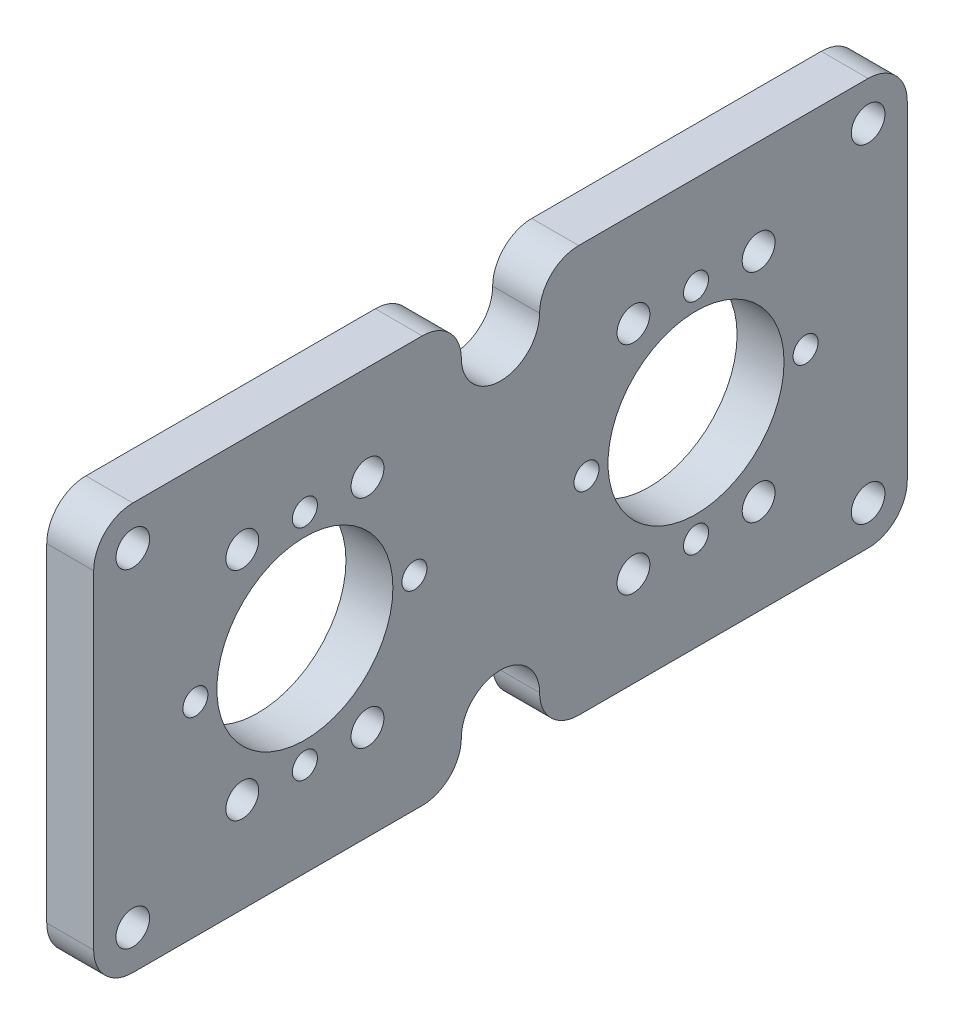
SolidWorks part; units mm, degrees
material "6061-T6 (SS)"
ref_plane "前视基准面" through (0, 0, 0) normal (0, 0, 1) x (1, 0, 0)
ref_plane "上视基准面" through (0, 0, 0) normal (0, 1, 0) x (1, 0, 0)
ref_plane "右视基准面" through (0, 0, 0) normal (1, 0, 0) x (0, 0, -1)
other "Configuration Table"
sketch "草图1" plane through (0, 0, 0) normal (1, 0, 0) x (0, 0, -1)
  line L0 (0, 0) -> (420, 0) construction
  line L1 (0, 0) -> (0, 110) construction
  line L2 (0, 110) -> (420, 110) construction
  line L3 (420, 110) -> (420, 0) construction
  line L4 (0, 15) -> (420, 15) construction
  line L5 (210, 110) -> (210, 0) construction
  line L6 (220.1351, 41.0331) -> (270.1351, 41.0331) construction
  line L7 (220.1351, 64.1271) -> (200.1351, 52.5801) construction
  line L8 (200.1351, 52.5801) -> (200.1351, 29.4861) construction
  line L9 (200.1351, 29.4861) -> (220.1351, 17.9391) construction
  line L10 (220.1351, 17.9391) -> (240.1351, 29.4861) construction
  line L11 (240.1351, 29.4861) -> (240.1351, 52.5801) construction
  line L12 (240.1351, 52.5801) -> (220.1351, 64.1271) construction
  line L13 (270.1351, 64.1271) -> (250.1351, 52.5801) construction
  line L14 (250.1351, 52.5801) -> (250.1351, 29.4861) construction
  line L15 (250.1351, 29.4861) -> (270.1351, 17.9391) construction
  line L16 (270.1351, 17.9391) -> (290.1351, 29.4861) construction
  line L17 (290.1351, 29.4861) -> (290.1351, 52.5801) construction
  line L18 (290.1351, 52.5801) -> (270.1351, 64.1271) construction
  line L19 (55.5, 52) -> (220.1351, 41.0331) construction
  line L20 (270.1351, 41.0331) -> (364.5, 52) construction
  line L21 (56.7695, 71.0578) -> (221.4046, 60.0909) construction
  line L22 (218.8656, 21.9754) -> (54.2305, 32.9422) construction
  line L23 (267.9302, 60.0054) -> (362.2951, 70.9723) construction
  line L24 (366.7049, 33.0277) -> (272.3401, 22.0608) construction
  line L30 (220.1351, 17.9391) -> (240.1351, 29.4861) construction
  line L31 (240.1351, 29.4861) -> (240.1351, 52.5801) construction
  line L32 (240.1351, 52.5801) -> (220.1351, 64.1271) construction
  line L33 (220.1351, 64.1271) -> (200.1351, 52.5801) construction
  line L34 (200.1351, 52.5801) -> (200.1351, 29.4861) construction
  line L35 (200.1351, 29.4861) -> (220.1351, 17.9391) construction
  line L36 (270.1351, 17.9391) -> (290.1351, 29.4861) construction
  line L37 (290.1351, 29.4861) -> (290.1351, 52.5801) construction
  line L38 (290.1351, 52.5801) -> (270.1351, 64.1271) construction
  line L39 (270.1351, 64.1271) -> (250.1351, 52.5801) construction
  line L40 (250.1351, 52.5801) -> (250.1351, 29.4861) construction
  line L41 (250.1351, 29.4861) -> (270.1351, 17.9391) construction
  line L42 (297.1351, 15.0331) -> (193.1351, 15.0331)
  line L43 (297.1351, 15.0331) -> (297.1351, 67.0331)
  line L44 (297.1351, 67.0331) -> (193.1351, 67.0331)
  line L45 (193.1351, 15.0331) -> (193.1351, 67.0331)
  line L46 (297.1351, 15.0331) -> (193.1351, 67.0331) construction
  line L47 (297.1351, 67.0331) -> (193.1351, 15.0331) construction
  circle A0 centre (55.5, 52) radius 52 construction
  circle A1 centre (364.5, 52) radius 52 construction
  circle A2 centre (220.1351, 41.0331) radius 20 construction
  circle A3 centre (270.1351, 41.0331) radius 20 construction
  circle A4 centre (220.1351, 41.0331) radius 19.1 construction
  circle A5 centre (270.1351, 41.0331) radius 19.1 construction
  circle A6 centre (55.5, 52) radius 19.1 construction
  circle A7 centre (364.5, 52) radius 19.1 construction
  circle A8 centre (55.5, 52) radius 4.025 construction
  circle A9 centre (364.5, 52) radius 4.025 construction
  circle A10 centre (220.1351, 41.0331) radius 20 construction
  circle A11 centre (270.1351, 41.0331) radius 20 construction
  circle A12 centre (220.1351, 41.0331) radius 11.25
  circle A13 centre (270.1351, 41.0331) radius 11.25
  point P42 (245.1351, 41.0331)
  dimension "D3" = 104
  dimension "D6" = 40
  dimension "D8" = 38.2
  dimension "D9" = 165
  dimension "D11" = 8.05
  dimension "D14" = 22.5
  dimension "D1" = 420
  dimension "D2" = 15
  dimension "D4" = 95
  dimension "D5" = 55.5
  dimension "D7" = 50
  dimension "D10" = 95
  dimension "D12" = 104
  dimension "D13" = 52
extrude "凸台-拉伸1" add sketch "草图1" along normal blind 6
sketch "草图2" plane through (6, 0, 0) normal (1, 0, 0) x (0, 0, -1)
  line L0 (245.1351, 67.0331) -> (245.1351, 62.0331) construction
  line L1 (297.1351, 67.0331) -> (193.1351, 67.0331) construction
  line L2 (193.1351, 67.0331) -> (193.1351, 15.0331) construction
  line L3 (240.1351, 62.0331) -> (240.1351, 67.0331)
  line L4 (240.1351, 67.0331) -> (250.1351, 67.0331)
  line L5 (250.1351, 67.0331) -> (250.1351, 62.0331)
  line L6 (193.1351, 41.0331) -> (297.1351, 41.0331) construction
  line L7 (297.1351, 15.0331) -> (297.1351, 67.0331) construction
  line L8 (245.1351, 15.0331) -> (245.1351, 20.0331) construction
  line L9 (250.1351, 15.0331) -> (250.1351, 20.0331)
  line L10 (240.1351, 15.0331) -> (250.1351, 15.0331)
  line L11 (240.1351, 20.0331) -> (240.1351, 15.0331)
  circle A0 centre (198.1351, 62.0331) radius 2.15
  circle A1 centre (245.1351, 62.0331) radius 2.15
  circle A2 centre (245.1351, 62.0331) radius 5
  circle A3 centre (292.1351, 62.0331) radius 2.15
  circle A4 centre (292.1351, 20.0331) radius 2.15
  circle A5 centre (245.1351, 20.0331) radius 5
  circle A6 centre (245.1351, 20.0331) radius 2.15
  circle A7 centre (198.1351, 20.0331) radius 2.15
  line M6 (193.1351, 15.0331) -> (297.1351, 15.0331)
  line M8 (297.1351, 67.0331) -> (193.1351, 67.0331)
  dimension "D1" = 4.3
  dimension "D2" = 5
  dimension "D3" = 5
  dimension "D5" = 10
  dimension "D4" = 5
extrude "切除-拉伸1" cut sketch "草图2" against normal blind 10 contours A0 | A7 | A5 A6 | L9 A5 L10 | A5 L11 M6 | A6 | A2 A1 | A1 | A2 L5 M8 | A2 L4 L3 | A3 | A4 region at (6, 65.4687, -241.6996) region at (6, 65.9163, -241.252) region at (6, 65.9163, -249.0183) region at (6, 16.15, -249.0183) region at (6, 16.5976, -248.5707) region at (6, 16.15, -241.252) region at (6, 62.0331, -198.1351) region at (6, 62.0331, -245.1351) region at (6, 62.0331, -292.1351) region at (6, 20.0331, -292.1351) region at (6, 20.0331, -245.1351) region at (6, 20.0331, -198.1351)
fillet "圆角2" radius 5 8 edges at (3, 15.0331, -240.1351) (3, 15.0331, -193.1351) (3, 67.0331, -240.1351) (3, 67.0331, -250.1351) (3, 67.0331, -297.1351) (3, 15.0331, -297.1351) (3, 15.0331, -250.1351) (3, 67.0331, -193.1351)
sketch "草图3" plane through (6, 0, 0) normal (1, 0, 0) x (0, 0, -1)
  line L0 (220.1351, 41.0331) -> (220.1351, 55.0331) construction
  line L1 (220.1351, 41.0331) -> (228.1351, 54.8895) construction
  line L2 (245.1351, 57.0331) -> (245.1351, 25.0331) construction
  line L3 (270.1351, 41.0331) -> (262.1351, 54.8895) construction
  line L4 (270.1351, 41.0331) -> (270.1351, 55.0331) construction
  circle A0 centre (220.1351, 55.0331) radius 1.6
  circle A1 centre (228.1351, 54.8895) radius 2.1
  circle A2 centre (236.1351, 41.0331) radius 2.1 construction
  circle A3 centre (228.1351, 27.1767) radius 2.1
  circle A4 centre (212.1351, 27.1767) radius 2.1
  circle A5 centre (204.1351, 41.0331) radius 2.1 construction
  circle A6 centre (212.1351, 54.8895) radius 2.1
  circle A7 centre (234.1351, 41.0331) radius 1.6
  circle A8 centre (220.1351, 27.0331) radius 1.6
  circle A9 centre (206.1351, 41.0331) radius 1.6
  arc A10 (240.1351, 62.0331) -> (250.1351, 62.0331) centre (245.1351, 62.0331) ccw construction
  arc A11 (250.1351, 20.0331) -> (240.1351, 20.0331) centre (245.1351, 20.0331) ccw construction
  circle A12 centre (286.1351, 41.0331) radius 2.1 construction
  circle A13 centre (254.1351, 41.0331) radius 2.1 construction
  circle A14 centre (284.1351, 41.0331) radius 1.6
  circle A15 centre (270.1351, 27.0331) radius 1.6
  circle A16 centre (256.1351, 41.0331) radius 1.6
  circle A17 centre (278.1351, 54.8895) radius 2.1
  circle A18 centre (278.1351, 27.1767) radius 2.1
  circle A19 centre (262.1351, 27.1767) radius 2.1
  circle A20 centre (262.1351, 54.8895) radius 2.1
  circle A21 centre (270.1351, 55.0331) radius 1.6
  point P18 (220.1351, 41.0331)
  point P26 (220.1351, 41.0331)
  point P53 (270.1351, 41.0331)
  point P54 (270.1351, 41.0331)
  dimension "D1" = 3.2
  dimension "D3" = 4.2
  dimension "D2" = 14
  dimension "D4" = 16
  dimension "D6" = 30
  dimension "D5" = 6
  dimension "D7" = 4
extrude "切除-拉伸2" cut sketch "草图3" against normal blind 10
sketch "Sketch1" plane through (0, 0, 0) normal (-1, 0, 0) x (0, 0, 1)
  circle A0 centre (-278.1351, 27.1767) radius 4
  circle A1 centre (-278.1351, 54.8895) radius 4
  circle A2 centre (-262.1351, 54.8895) radius 4
  circle A3 centre (-262.1351, 27.1767) radius 4
  circle A4 centre (-228.1351, 54.8895) radius 4
  circle A5 centre (-212.1351, 54.8895) radius 4
  circle A6 centre (-212.1351, 27.1767) radius 4
  circle A7 centre (-228.1351, 27.1767) radius 4
  dimension "D1" = 8
extrude "Cut-Extrude1" cut sketch "Sketch1" against normal blind 2
